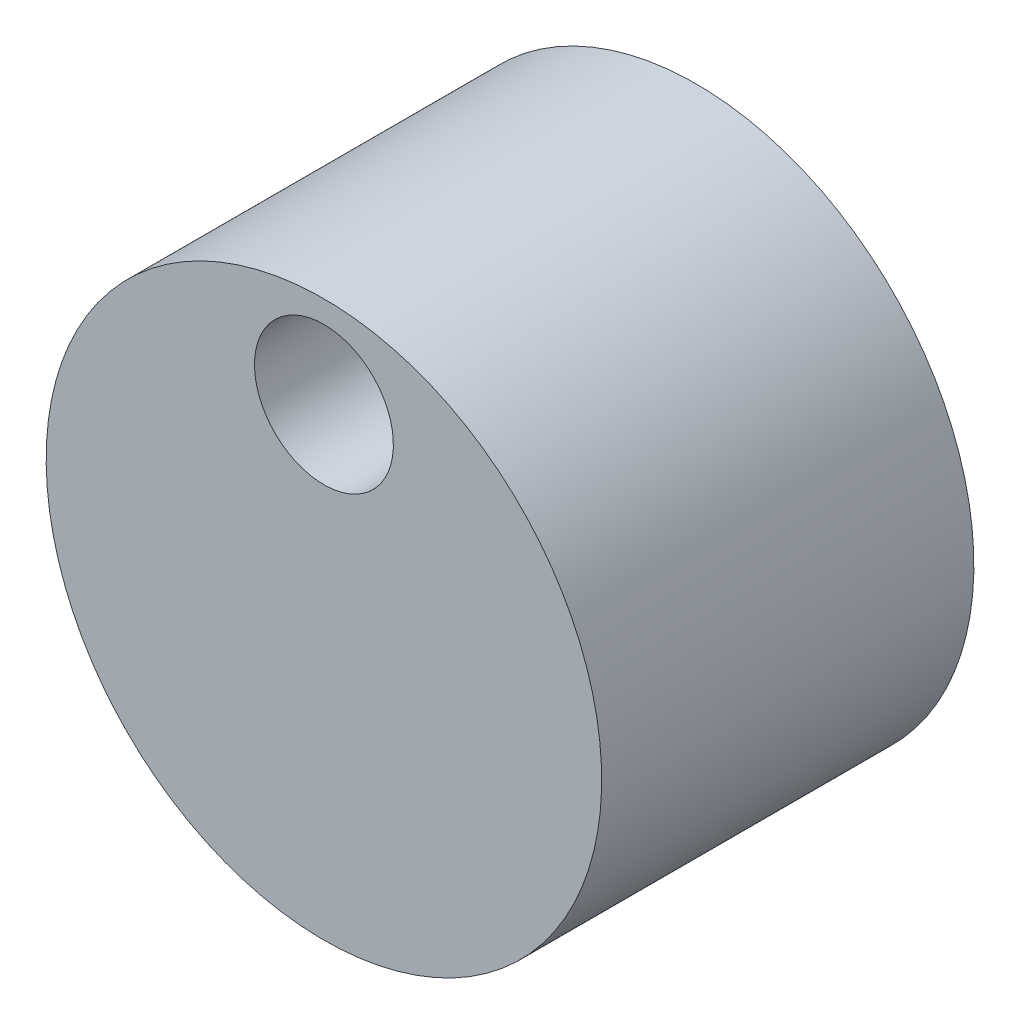
SolidWorks part; units mm, degrees
ref_plane "Plan de face" through (0, 0, 0) normal (0, 0, 1) x (1, 0, 0)
ref_plane "Plan de dessus" through (0, 0, 0) normal (0, 1, 0) x (1, 0, 0)
ref_plane "Plan de droite" through (0, 0, 0) normal (1, 0, 0) x (0, 0, -1)
sketch "Esquisse2" plane through (0, 0, 0) normal (0, 0, 1) x (1, 0, 0)
  line L0 (0, 0) -> (0, 8.509) construction
  ellipse E0 centre (0, 0) end of major axis (-9.6375, -8.271) minor radius 12.7
  ellipse E1 centre (0, 8.509) end of major axis (2.6707, 10.226) minor radius 3.175
extrude "Boss.-Extru.2" add sketch "Esquisse2" along normal blind 17.018
